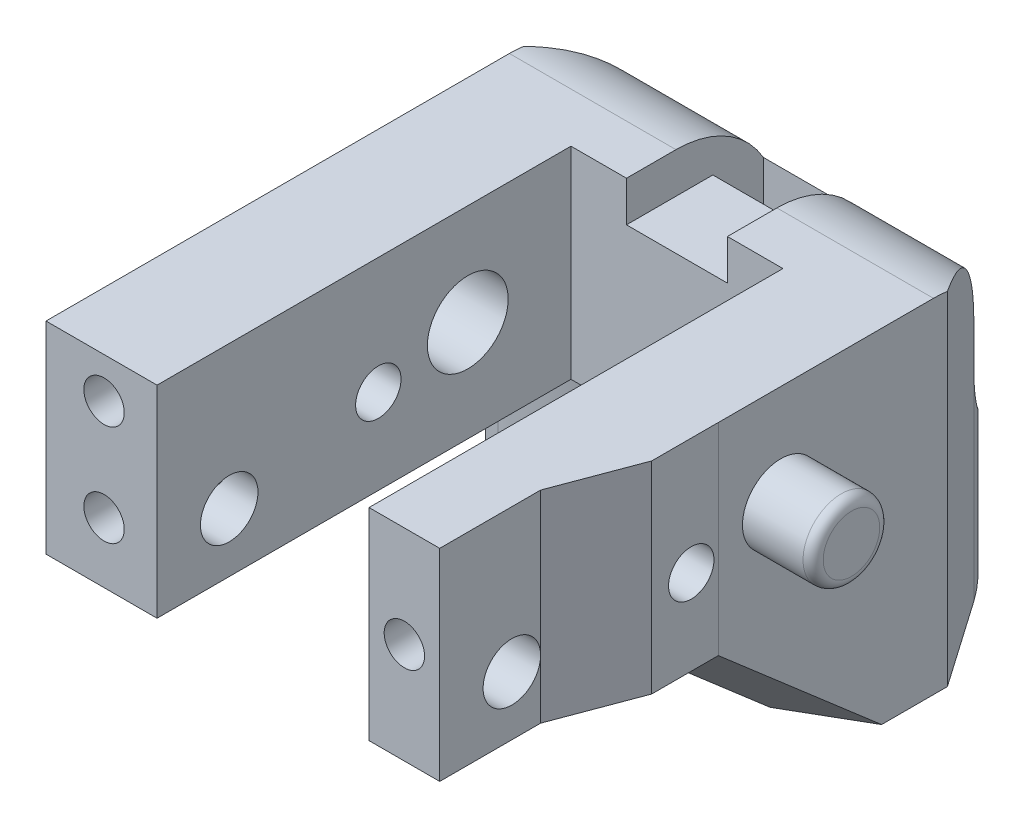
SolidWorks part; units mm, degrees
material "ABS"
ref_plane "Front Plane" through (0, 0, 0) normal (0, 0, 1) x (1, 0, 0)
ref_plane "Top Plane" through (0, 0, 0) normal (0, 1, 0) x (1, 0, 0)
ref_plane "Right Plane" through (0, 0, 0) normal (1, 0, 0) x (0, 0, -1)
sketch "Sketch1" plane through (0, 0, 0) normal (0, 1, 0) x (1, 0, 0)
  line L0 (-15.5, -37) -> (-10, -37)
  line L2 (-15.5, -37) -> (-15.5, 10)
  line L3 (-15.5, 10) -> (21, 10)
  line L4 (21, -19) -> (21, 10)
  line L5 (-10, -37) -> (-10, 4)
  line L6 (-10, 4) -> (11, 4)
  line L7 (11, 4) -> (11, -37)
  line L9 (21, -19) -> (18, -27)
  line L10 (18, -27) -> (18, -37)
  line L11 (11, -37) -> (18, -37)
  point P0 (0, 0)
  dimension "D1" = 36.5
  dimension "D2" = 7
  dimension "D3" = 21
  dimension "D4" = 10
  dimension "D5" = 21
  dimension "D6" = 41
  dimension "D7" = 47
  dimension "D8" = 8
  dimension "D9" = 5.5
  dimension "D10" = 10
extrude "Boss-Extrude1" add sketch "Sketch1" along normal blind 20
sketch "Sketch6" plane through (-15.5, 0, 0) normal (-1, 0, 0) x (0, 0, 1)
  line L1 (15, 0) -> (-10, 0)
  line L2 (15, 0) -> (15, 20)
  line L3 (15, 20) -> (-10, 20)
  line L4 (-10, 0) -> (-10, 20)
  line L5 (-10, 20) -> (-10, 0) construction
  line L7 (-10, 0) -> (37, 0) construction
  line L8 (-10, 20) -> (37, 20) construction
  dimension "D3" = 25
extrude "Boss-Extrude5" add sketch "Sketch6" along normal blind 5.5
sketch "Sketch20" plane through (0, 20, 0) normal (0, 1, 0) x (1, 0, 0)
  line L4 (-21, 6.5542) -> (14, 6.5542)
  line L11 (21.0063, -12.4007) -> (21.0063, 10.2821)
  line L12 (21.0063, 10.2821) -> (15.0032, 18.9016)
  line L13 (15.0032, 18.9016) -> (-14.9968, 18.9016)
  line L14 (-14.9968, 18.9016) -> (-21, 10.2821)
  line L15 (-21, 10) -> (-21, -15) construction
  line L16 (-21, 10.2821) -> (-21, 6.5542)
  line L18 (14, 6.5542) -> (14, -16.4458)
  line L20 (14, -16.4458) -> (21.0063, -12.4007)
  dimension "D2" = 23
  dimension "D4" = 30
  dimension "D8" = 35
  dimension "D9" = 60
  dimension "D1" = 6.0032
  dimension "D3" = 6.0032
  dimension "D5" = 8.6195
  dimension "D6" = 8.6195
  dimension "D7" = 3.7279
extrude "Boss-Extrude11" add sketch "Sketch20" along normal blind 14 and the other way up to surface (20 mm away) other way up to face at (0.5833, 0, 16.3333)
sketch "Sketch4" plane through (0, 20, 0) normal (0, 1, 0) x (1, 0, 0)
  line L2 (-10, 4) -> (11, 4) construction
  line L4 (-10, -37) -> (-10, 4) construction
  circle A6 centre (-4.375, 8) radius 2
  circle A7 centre (5.375, 8) radius 2
  dimension "D1" = 4
  dimension "D2" = 4
  dimension "D3" = 9.75
  dimension "D4" = 5.625
extrude "Cut-Extrude1" cut sketch "Sketch4" against normal blind 10
sketch "Sketch24" plane through (0, 34, 0) normal (0, 1, 0) x (1, 0, 0)
  line L0 (21.0063, 10.2821) -> (15.0032, 18.9016) construction
  line L1 (-14.9968, 18.9016) -> (-14.4209, 19.7285)
  line L2 (-21, 10.2821) -> (-21, 6.5542) construction
  line L3 (-14.9968, 18.9016) -> (-21, 10.2821) construction
  line L4 (21.0063, 10.2821) -> (15.0032, 18.9016)
  line L6 (-21, 10.2821) -> (-21, 6.5542)
  line L7 (-14.9968, 18.9016) -> (-21, 10.2821)
  line L11 (-21, 6.5542) -> (14, 6.5542) construction
  line L14 (-21, 6.5542) -> (21.0063, 6.5542)
  line L16 (21.0063, 10.2821) -> (21.0063, 6.5542)
  line L17 (21.0063, -12.4007) -> (21.0063, 10.2821) construction
  arc A3 (8.6131, 24.6437) -> (-14.4209, 19.7285) centre (-0.0555, 8.8374) ccw
  arc A4 (8.6131, 24.6437) -> (15.0032, 18.9016) centre (-0.4313, 8.152) cw
  dimension "D3" = 18.0273
  dimension "D4" = 18.8089
  dimension "D1" = 0.5759
  dimension "D2" = 1.0077
extrude "Boss-Extrude13" add sketch "Sketch24" against normal blind 12
fillet "Fillet11" radius 7.95 1 edges at (0.0032, 22, -18.9016)
sketch "Sketch22" plane through (0, 34, 0) normal (0, 1, 0) x (1, 0, 0)
  line L2 (-21, 10.2821) -> (-21, 6.5542) construction
  line L3 (-21, 6.5542) -> (14, 6.5542) construction
  circle A0 centre (-14.7203, 13.3514) radius 2
  circle A1 centre (-3.0673, 22.5813) radius 2
  dimension "D1" = 4
  dimension "D2" = 6.2797
  dimension "D3" = 6.7972
  dimension "D4" = 17.9327
  dimension "D5" = 16.0271
extrude "Cut-Extrude6" cut sketch "Sketch22" against normal blind 10
chamfer "Chamfer1" distance 14 angle 45 1 edges at (17.5032, 34, 14.4233)
sketch "Sketch26" plane through (-21, 0, 0) normal (-1, 0, 0) x (0, 0, 1)
  line L0 (15, 0) -> (37, 0)
  line L2 (37, 0) -> (37, 20)
  line L3 (37, 20) -> (15, 20)
  line L4 (15, 0) -> (15, 20) construction
  line L5 (15, 20) -> (15, 0)
extrude "Boss-Extrude14" add sketch "Sketch26" against normal up to surface (11 mm away) up to face at (-10, 10, 16.5)
sketch "Sketch25" plane through (-21, 0, 0) normal (-1, 0, 0) x (0, 0, 1)
  line L0 (11.8689, 14.9312) -> (31.15, 18.331)
  line L1 (13.2147, 7.2989) -> (32.4958, 10.6987)
  line L2 (32.4958, 10.6987) -> (31.15, 18.331) construction
  line L3 (6.2179, 10) -> (31.8229, 14.5149) construction
  line L4 (-10.2821, 0) -> (37, 0) construction
  line L5 (6.2179, 10) -> (6.2179, 38.8588) construction
  line L7 (-10.2821, 34) -> (-10.2821, 0) construction
  arc A1 (11.8689, 14.9312) -> (13.2147, 7.2989) centre (6.2179, 10) ccw
  arc A3 (31.15, 18.331) -> (32.4958, 10.6987) centre (31.8229, 14.5149) cw
  dimension "D2" = 7.75
  dimension "D1" = 7.5
  dimension "D4" = 7.75
  dimension "D3" = 26
  dimension "D5" = 80
  dimension "D7" = 10
  dimension "D6" = 16.5
  dimension "D8" = 3.875
extrude "Cut-Extrude7" cut sketch "Sketch25" against normal blind 2.5
sketch "Sketch27" plane through (-18.5, 0, 0) normal (-1, 0, 0) x (0, 0, 1)
  line L0 (6.2179, 10) -> (31.8229, 14.5149) construction
  circle A0 centre (6.2179, 10) radius 4
  circle A1 centre (15.0812, 11.5628) radius 1.15
  circle A4 centre (29.8533, 14.1676) radius 1.6
  dimension "D1" = 8
  dimension "D3" = 2.3
  dimension "D4" = 3.2
  dimension "D2" = 9
  dimension "D5" = 2
extrude "Cut-Extrude8" cut sketch "Sketch27" against normal up to next
sketch "Sketch28" plane through (-21, 0, 0) normal (-1, 0, 0) x (0, 0, 1)
  line L4 (-0.0283, 0.7779) -> (-3.1977, 15.9504)
  line L6 (13.3704, 7.7433) -> (11.8689, 14.9312) construction
  line L10 (-3.1977, 15.9504) -> (10.5064, 18.8131)
  line L11 (10.5064, 18.8131) -> (17.2487, 15.8798)
  line L13 (31.15, 18.331) -> (11.8689, 14.9312) construction
  line L14 (17.2487, 15.8798) -> (18.6801, 9.0277)
  line L16 (18.6801, 9.0277) -> (13.6759, 3.6406)
  line L17 (13.6759, 3.6406) -> (-0.0283, 0.7779)
  arc A0 (11.8689, 14.9312) -> (13.2147, 7.2989) centre (6.2179, 10) ccw construction
  circle A1 centre (6.2179, 10) radius 4 construction
  dimension "D1" = 15.5
  dimension "D2" = 7.75
  dimension "D3" = 8
  dimension "D4" = 14
  dimension "D5" = 14
  dimension "D6" = 6
  dimension "D7" = 7
extrude "Cut-Extrude9" cut sketch "Sketch28" against normal blind 2.5
sketch "Sketch31" plane through (-18.5, 0, 0) normal (-1, 0, 0) x (0, 0, 1)
  circle A0 centre (6.2179, 10) radius 4
  circle A1 centre (6.2179, 10) radius 1.65
  circle A2 centre (6.2179, 10) radius 4 construction
  dimension "D2" = 3.3
extrude "Boss-Extrude15" add sketch "Sketch31" along normal blind 1 and the other way blind 2
sketch "Sketch32" plane through (-10, 0, 0) normal (1, 0, 0) x (0, 0, -1)
  circle A0 centre (-29.8533, 14.1676) radius 2.85
  circle A3 centre (-15.0812, 11.5628) radius 2.25
  point P5 (-27.8837, 13.8203)
  dimension "D1" = 5.7
  dimension "D2" = 4.5
extrude "Cut-Extrude12" cut sketch "Sketch32" against normal blind 7 and the other way up to next
sketch "Sketch33" plane through (21.0063, 0, 0) normal (1, 0, 0) x (0, 0, -1)
  circle A0 centre (-6.2179, 10) radius 3.8
  circle A1 centre (-6.2179, 10) radius 1.65 construction
  dimension "D1" = 7.6
extrude "Boss-Extrude17" add sketch "Sketch33" along normal blind 7
fillet "Fillet17" radius 1 1 edges at (28.0063, 10, 2.4179)
sketch "Sketch35" plane through (0, 34, 0) normal (0, 1, 0) x (1, 0, 0)
  line L0 (-21, 6.5542) -> (14, 6.5542) construction
  line L1 (-19.8, 6.5542) -> (14, 6.5542)
  line L3 (-9.8027, 12.5542) -> (14, 12.5542)
  line L4 (14, 6.5542) -> (14, 12.5542)
  line L7 (14, 6.5542) -> (14, -0.28) construction
  arc A0 (-19.8, 6.5542) -> (-12.285, 9.9568) centre (-19.8, 16.5542) ccw
  arc A1 (-12.285, 9.9568) -> (-9.8027, 12.5542) centre (19.6614, -18.0889) cw
  dimension "D3" = 42.5104
  dimension "D4" = 10
  dimension "D5" = 8.2494
  dimension "D1" = 23.8027
  dimension "D2" = 6
  dimension "D6" = 9.9972
extrude "Cut-Extrude13" cut sketch "Sketch35" against normal up to surface (14 mm away) up to face at (4.25, 20, 11.0396)
sketch "Sketch36" plane through (0, 0, 37) normal (0, 0, 1) x (1, 0, 0)
  line L0 (11, 20) -> (11, 0) construction
  line L1 (11, 20) -> (18, 20) construction
  line L2 (-21, 0) -> (-21, 20) construction
  line L6 (-21, 20) -> (-10, 20) construction
  circle A0 centre (-15.25, 14) radius 2
  circle A1 centre (14.5, 10) radius 2
  circle A2 centre (-15.25, 4) radius 2
  dimension "D3" = 4
  dimension "D1" = 5.75
  dimension "D2" = 3.5
  dimension "D4" = 10
  dimension "D5" = 6
  dimension "D6" = 5.75
  dimension "D7" = 10
extrude "Cut-Extrude14" cut sketch "Sketch36" against normal blind 10
fillet "Fillet18" radius 10 1 edges at (0.0032, 0, -18.9016)
sketch "Sketch37" plane through (21, 0, 0) normal (1, 0, 0) x (0, 0, -1)
  line L0 (-6.2179, 10) -> (6.304, 10) construction
  line L1 (4, 20) -> (4, 0) construction
  line L2 (-1.7179, 13) -> (4, 13)
  line L3 (-1.7179, 13) -> (-1.7179, 7)
  line L4 (-1.7179, 7) -> (4, 7)
  line L5 (4, 13) -> (4, 7)
  point P7 (0.043, 10)
  dimension "D1" = 6
  dimension "D2" = 3
  dimension "D4" = 4.5
extrude "Cut-Extrude16" cut sketch "Sketch37" against normal up to next
chamfer "Chamfer2" distance 7 angle 45 1 edges at (11, 10, 1.7179)
sketch "Sketch38" plane through (0, 0, 0) normal (0, -1, 0) x (1, 0, 0)
  line L0 (-10, -4) -> (11, -4) construction
  line L1 (-4.5, -4) -> (5.5, -4)
  line L2 (-4.5, -4) -> (-4.5, -24)
  line L3 (-4.5, -24) -> (5.5, -24)
  line L4 (5.5, -4) -> (5.5, -24)
  line L5 (-10, 37) -> (-10, -4) construction
  dimension "D1" = 10
  dimension "D2" = 5.5
  dimension "D3" = 20
extrude "Cut-Extrude17" cut sketch "Sketch38" against normal blind 4
sketch "Sketch39" plane through (0, 34, 0) normal (0, 1, 0) x (1, 0, 0)
  line L0 (14, 12.5542) -> (-9.8027, 12.5542) construction
  line L1 (-4.5, 12.5542) -> (5.5, 12.5542)
  line L2 (-4.5, 12.5542) -> (-4.5, 17.5542)
  line L3 (-4.5, 17.5542) -> (5.5, 17.5542)
  line L4 (5.5, 12.5542) -> (5.5, 17.5542)
  line L5 (5.5, 16.9016) -> (5.5, 4) construction
  line L6 (-4.5, 4) -> (-4.5, 16.9016) construction
  dimension "D1" = 5
extrude "Cut-Extrude19" cut sketch "Sketch39" against normal up to next
ref_plane "Plane1" through (0, -10, 0) normal (0, -1, 0) x (-1, 0, 0)
mirror "Mirror1" about plane through (0, -10, 0) normal (0, -1, 0) of bodies 140
sketch "Sketch40" plane through (0, 0, -18.9016) normal (0, 0, -1) x (-1, 0, 0)
  line L1 (30.516, -2.8705) -> (-40.4997, -2.8705)
  line L2 (30.516, -2.8705) -> (30.516, 39.4965)
  line L3 (30.516, 39.4965) -> (-40.4997, 39.4965)
  line L4 (-40.4997, -2.8705) -> (-40.4997, 39.4965)
extrude "Cut-Extrude20" cut sketch "Sketch40" against normal through all both and the other way through all
equation "\"D4@Sketch4\"=(21-\"D3@Sketch4\")/2"
equation "\"D2@Sketch37\"=\"D1@Sketch37\"/2"
equation "\"D3@Sketch20\"=\"D1@Sketch20\""
equation "\"D6@Sketch20\"=\"D5@Sketch20\""
equation "\"D5@Sketch28\"=\"D4@Sketch28\""
equation "\"D2@Sketch25\"=\"D4@Sketch25\""
equation "\"D8@Sketch25\"=\"D4@Sketch25\"/2"
